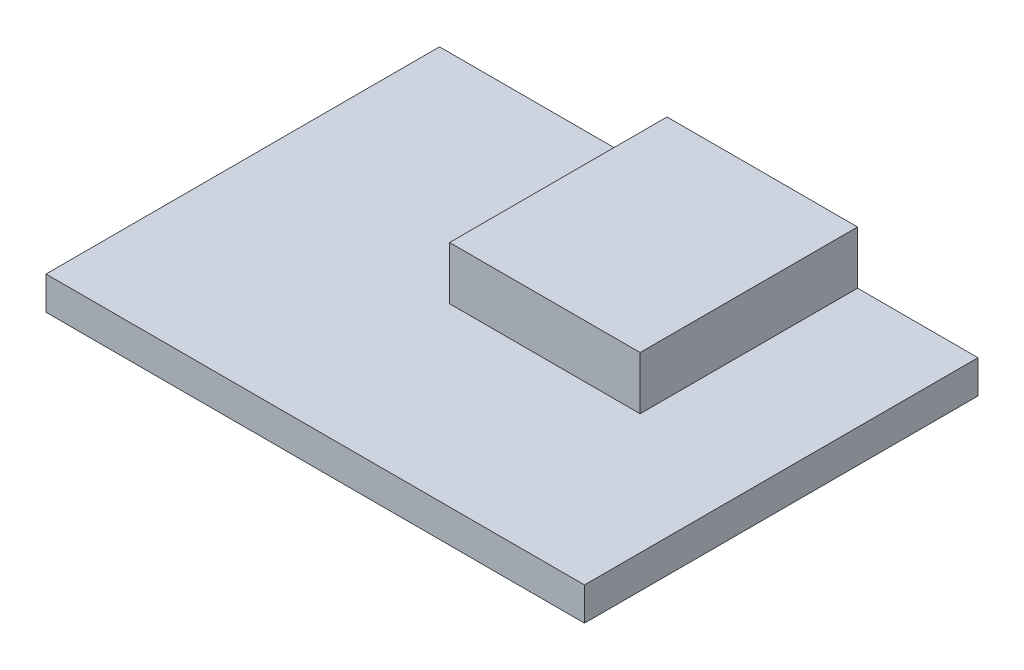
SolidWorks part; units mm, degrees
ref_plane "Front Plane" through (0, 0, 0) normal (0, 0, 1) x (1, 0, 0)
ref_plane "Top Plane" through (0, 0, 0) normal (0, 1, 0) x (1, 0, 0)
ref_plane "Right Plane" through (0, 0, 0) normal (1, 0, 0) x (0, 0, -1)
ref_axis "X-Axis" through (-88.99, 0, 0) along (1, 0, 0)
ref_axis "Y-Axis" through (0, 55, 0) along (0, -1, 0)
ref_axis "Z-Axis" through (0, 0, -88.99) along (0, 0, 1)
sketch "Sketch1" plane through (0, 0, 0) normal (0, 1, 0) x (1, 0, 0)
  line L1 (-13, -9.5) -> (13, -9.5)
  line L2 (-13, -9.5) -> (-13, 9.5)
  line L3 (-13, 9.5) -> (13, 9.5)
  line L4 (13, -9.5) -> (13, 9.5)
  line L5 (-13, -9.5) -> (13, 9.5) construction
  line L6 (-13, 9.5) -> (13, -9.5) construction
  point P0 (0, 0)
  dimension "D1" = 26
  dimension "D2" = 19
extrude "Boss-Extrude1" add sketch "Sketch1" along normal blind 1.6
sketch "Sketch2" plane through (0, 1.6, 0) normal (0, 1, 0) x (1, 0, 0)
  line L0 (13, 9.5) -> (-13, 9.5) construction
  line L1 (-2.0151, 9.5) -> (7.1849, 9.5)
  line L2 (-2.0151, 9.5) -> (-2.0151, -1)
  line L3 (-2.0151, -1) -> (7.1849, -1)
  line L4 (7.1849, 9.5) -> (7.1849, -1)
  dimension "D1" = 9.2
  dimension "D2" = 10.5
extrude "Boss-Extrude2" add sketch "Sketch2" along normal blind 2.56
